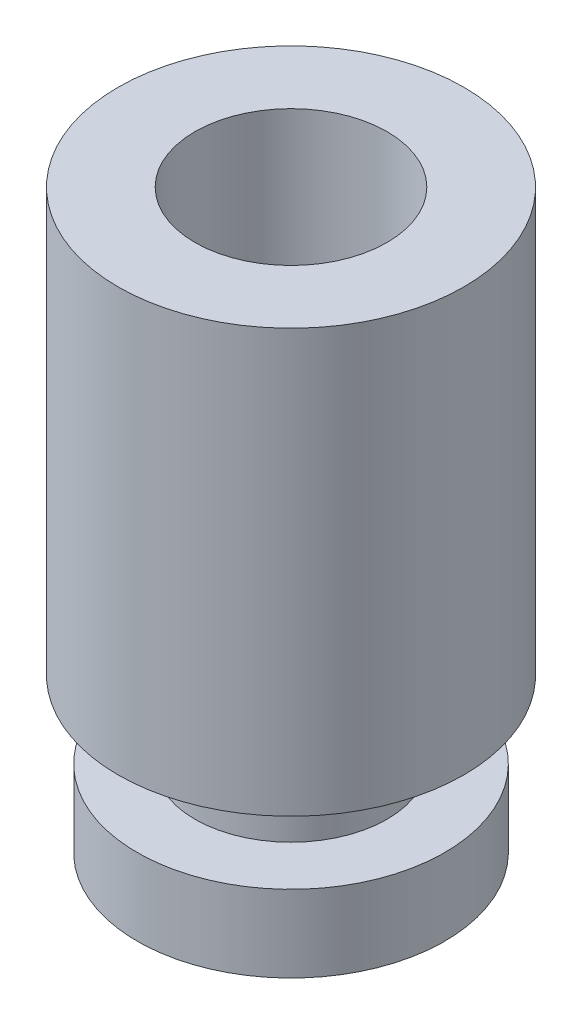
SolidWorks part; units mm, degrees
ref_plane "Front Plane" through (0, 0, 0) normal (0, 0, 1) x (1, 0, 0)
ref_plane "Top Plane" through (0, 0, 0) normal (0, 1, 0) x (1, 0, 0)
ref_plane "Right Plane" through (0, 0, 0) normal (1, 0, 0) x (0, 0, -1)
sketch "Sketch1" plane through (0, 0, 0) normal (0, 1, 0) x (1, 0, 0)
  circle A0 centre (-0.522, 0.5111) radius 1.25
  circle A1 centre (-0.522, 0.5111) radius 2.25
  dimension "D1" = 2.5
  dimension "D2" = 4.5
extrude "Boss-Extrude1" add sketch "Sketch1" along normal blind 5.5 contours A1
extrude "Boss-Extrude2" add sketch "Sketch1<3>" along normal blind 1 contours A0 region at (-0.522, 0, -0.5111)
sketch "Sketch1<3>" plane through (0, 0, 0) normal (0, 1, 0) x (1, 0, 0) same geometry as "Sketch1"
sketch "Sketch5" plane through (0, 0, 0) normal (0, -1, 0) x (1, 0, 0)
  circle A3 centre (-0.522, -0.5111) radius 1.25
  dimension "D1" = 2.5
extrude "Boss-Extrude3" add sketch "Sketch5" along normal blind 1 contours A3
sketch "Sketch6" plane through (0, -1, 0) normal (0, -1, 0) x (1, 0, 0)
  circle A0 centre (-0.522, -0.5111) radius 2
  dimension "D1" = 4
extrude "Boss-Extrude4" add sketch "Sketch6" along normal blind 1
sketch "Sketch8" plane through (0, -2, 0) normal (0, -1, 0) x (-1, 0, 0)
  circle A0 centre (0.522, 0.5111) radius 1.5
  dimension "D1" = 3
sketch "Sketch11" plane through (0, 5.5, 0) normal (0, 1, 0) x (1, 0, 0)
  text T0 "VIII" font "Century Gothic" height in points 5
sketch "Sketch12" plane through (0, 5.5, 0) normal (0, 1, 0) x (1, 0, 0)
  circle A0 centre (-0.522, 0.5111) radius 1.25
  dimension "D1" = 2.5
extrude "Cut-Extrude1" cut sketch "Sketch12" against normal blind 5
